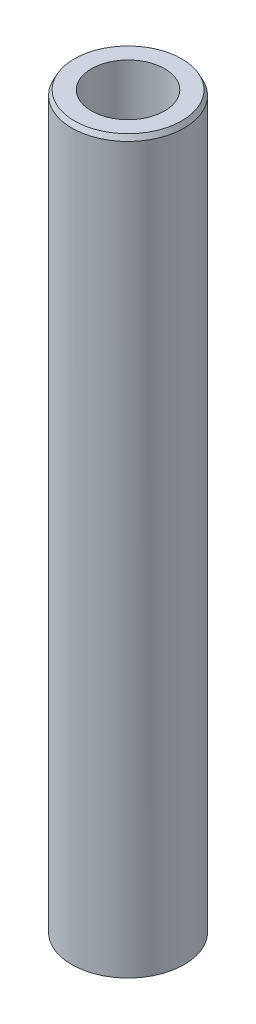
SolidWorks part; units mm, degrees
ref_plane "Front Plane" through (0, 0, 0) normal (0, 0, 1) x (1, 0, 0)
ref_plane "Top Plane" through (0, 0, 0) normal (0, 1, 0) x (1, 0, 0)
ref_plane "Right Plane" through (0, 0, 0) normal (1, 0, 0) x (0, 0, -1)
sketch "Sketch1" plane through (0, 0, 0) normal (0, 1, 0) x (1, 0, 0)
  circle A0 centre (0, 0) radius 32.5
  dimension "SHAFT_OD" = 65
extrude "Boss-Extrude1" add sketch "Sketch1" along normal blind 422.8368
sketch "Sketch2" plane through (0, 0, 0) normal (0, 1, 0) x (1, 0, 0)
  circle A0 centre (0, 0) radius 21.1536
  dimension "BORE_D" = 42.3072
extrude "Cut-Extrude1" cut sketch "Sketch2" along normal through all
chamfer "Chamfer1" distance 2.865 angle 27.002 2 edges at (0, 422.8368, 32.5) (0, 0, 32.5) first distance on face at (0, 422.8368, 32.5) first distance on face at (0, 0, 21.1536)
